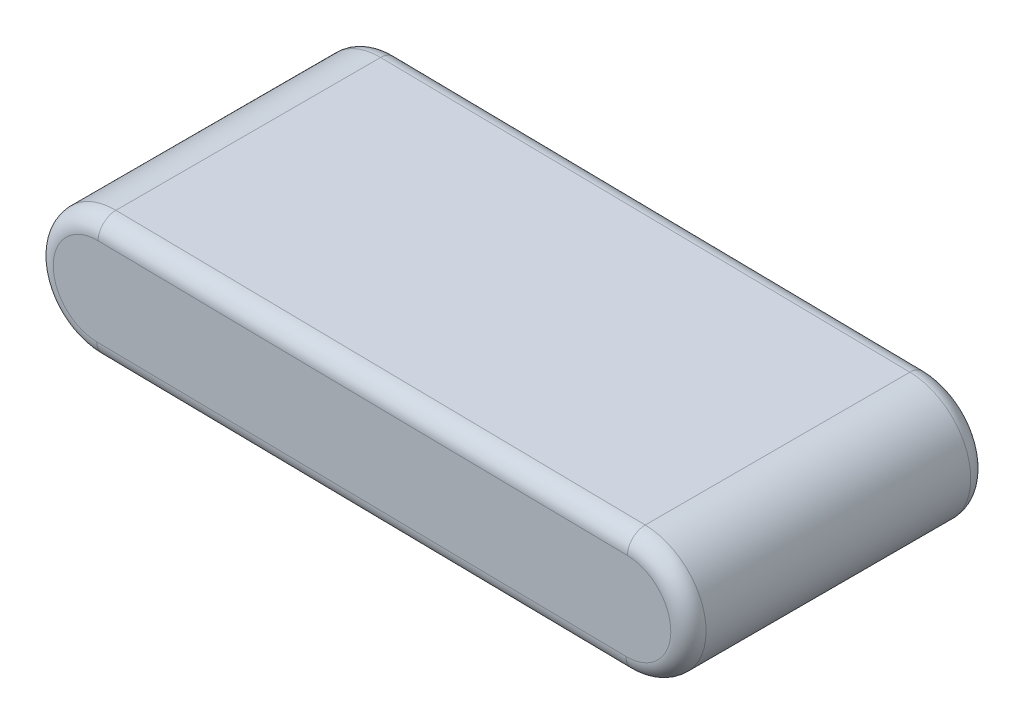
SolidWorks part; units mm, degrees
ref_plane "Plano frontal" through (0, 0, 0) normal (0, 0, 1) x (1, 0, 0)
ref_plane "Plano superior" through (0, 0, 0) normal (0, 1, 0) x (1, 0, 0)
ref_plane "Plano direito" through (0, 0, 0) normal (1, 0, 0) x (0, 0, -1)
sketch "Esboço1" plane through (0, 0, 0) normal (0, 0, 1) x (1, 0, 0)
  line L0 (-15, 0.2234) -> (15, -0.2234) construction
  line L1 (-15, 0.2234) -> (15, -0.2234) construction
  line L2 (-14.9479, 3.723) -> (15.0521, 3.2762)
  line L3 (-15.0521, -3.2762) -> (14.9479, -3.723)
  arc A0 (-14.9479, 3.723) -> (-15.0521, -3.2762) centre (-15, 0.2234) ccw
  arc A1 (14.9479, -3.723) -> (15.0521, 3.2762) centre (15, -0.2234) ccw
  point P0 (0, 0)
  dimension "D2" = 3.5
  dimension "D1" = 30
extrude "Ressalto-extrusão1" add sketch "Esboço1" along normal blind 17
fillet "Filete1" radius 1 8 edges at (18.4996, -0.2756, 0) (-0.0521, -3.4996, 0) (-18.4996, 0.2756, 0) (18.4996, -0.2756, 17) (-0.0521, -3.4996, 17) (-18.4996, 0.2756, 17) (0.0521, 3.4996, 0) (0.0521, 3.4996, 17)
sketch "Esboço2" plane through (0, 0, 17) normal (0, 0, 1) x (1, 0, 0)
  line L0 (-18.4996, 0.2756) -> (18.4996, -0.2756) construction
  line L2 (-14.9479, 3.723) -> (15.0521, 3.2762) construction
  line L3 (0.0521, 3.4996) -> (-0.0521, -3.4996) construction
  line L4 (14.9479, -3.723) -> (-15.0521, -3.2762) construction
  arc A0 (-14.9479, 3.723) -> (-15.0521, -3.2762) centre (-15, 0.2234) ccw construction
  arc A1 (14.9479, -3.723) -> (15.0521, 3.2762) centre (15, -0.2234) ccw construction
